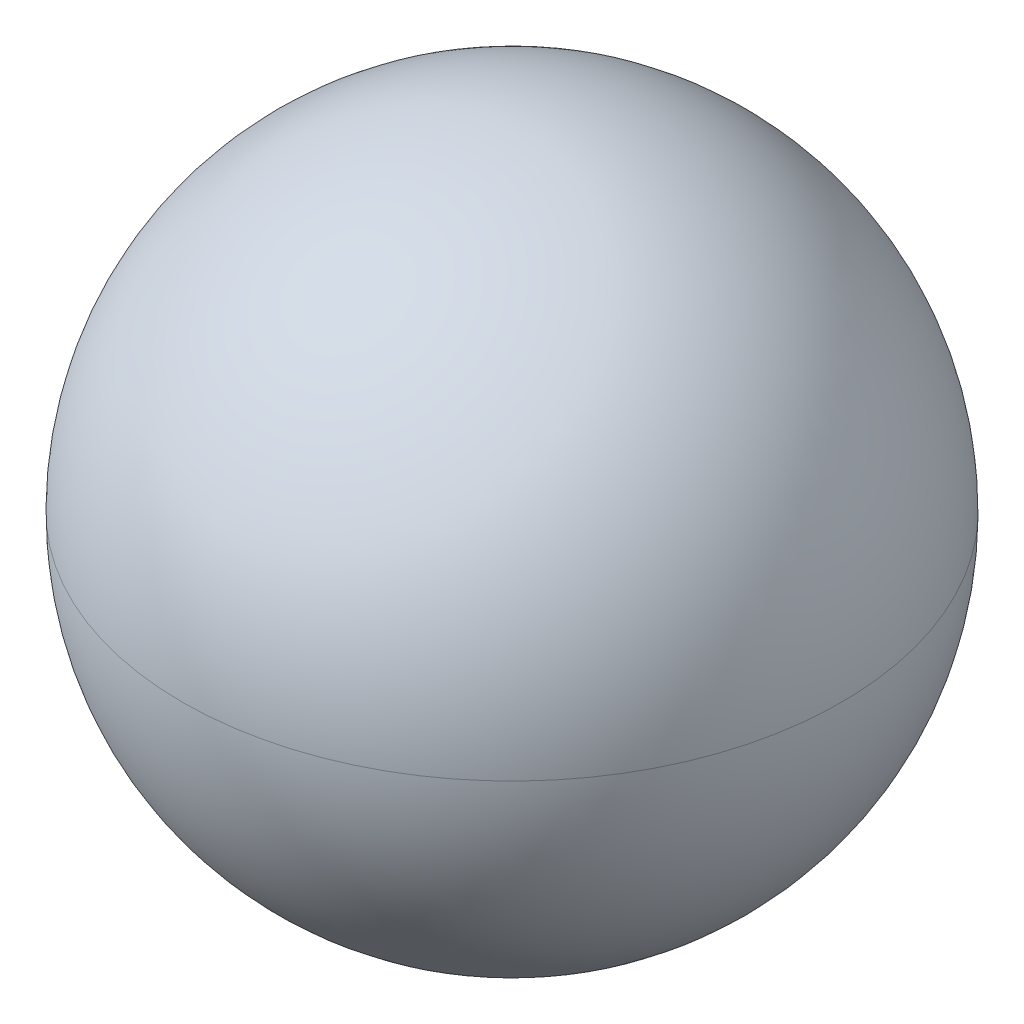
SolidWorks part; units mm, degrees
ref_plane "Front Plane" through (0, 0, 0) normal (0, 0, 1) x (1, 0, 0)
ref_plane "Top Plane" through (0, 0, 0) normal (0, 1, 0) x (1, 0, 0)
ref_plane "Right Plane" through (0, 0, 0) normal (1, 0, 0) x (0, 0, -1)
sketch "Sketch1" plane through (0, 0, 0) normal (0, 1, 0) x (1, 0, 0)
  circle A0 centre (0, 0) radius 381
  dimension "D1" = 762
extrude "Boss-Extrude1" add sketch "Sketch1" along normal blind 762
fillet "Fillet1" radius 381 2 edges at (0, 0, 381) (0, 762, 381)
shell "Shell2" thickness 3.175
